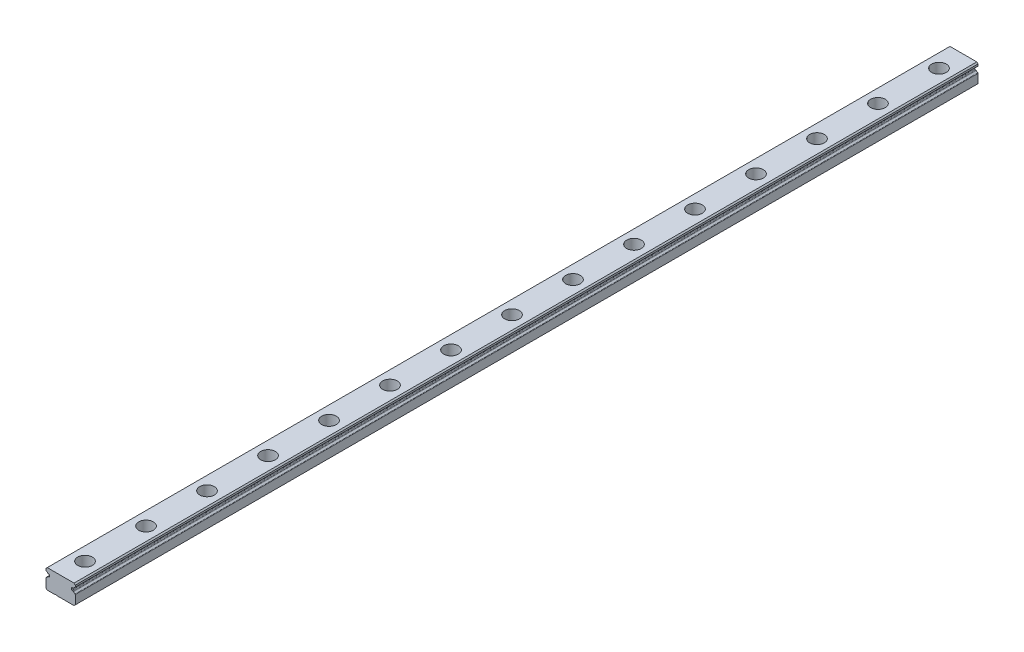
SolidWorks part; units mm, degrees
ref_plane "Front Plane" through (0, 0, 0) normal (0, 0, 1) x (1, 0, 0)
ref_plane "Top Plane" through (0, 0, 0) normal (0, 1, 0) x (1, 0, 0)
ref_plane "Right Plane" through (0, 0, 0) normal (1, 0, 0) x (0, 0, -1)
sketch "Sketch1" plane through (0, 0, 0) normal (0, 0, 1) x (1, 0, 0)
  line B0 (5.5, -8) -> (6, -7.5)
  line B1 (6, -7.5) -> (6, -3.8579)
  line B2 (5.0738, -3.0055) -> (4.7282, -2.9753)
  line B3 (4.5, -2.7262) -> (4.5, -2.2738)
  line B4 (4.7282, -2.0247) -> (5.0948, -1.9927)
  line B5 (6, -1.1746) -> (6, -0.5)
  line B6 (6, -0.5) -> (5.5, 0)
  line B7 (5.5, 0) -> (-5.5, 0)
  line B8 (-5.5, 0) -> (-6, -0.5)
  line B9 (-6, -0.5) -> (-6, -1.1746)
  line B10 (-5.0948, -1.9927) -> (-4.7282, -2.0247)
  line B11 (-4.5, -2.2738) -> (-4.5, -2.7262)
  line B12 (-4.7282, -2.9753) -> (-5.0738, -3.0055)
  line B13 (-6, -3.8579) -> (-6, -7.5)
  line B14 (-6, -7.5) -> (-5.5, -8)
  line B15 (-5.5, -8) -> (-2.4, -8)
  line B16 (-1.6, -8) -> (5.5, -8)
  line B17 (0, 0) -> (0, -8) construction
  arc B18 (6, -3.8579) -> (5.8448, -3.6266) centre (5.75, -3.8579) ccw
  arc B19 (5.2672, -3.1272) -> (5.8448, -3.6266) centre (6.3, -2.5162) ccw
  arc B20 (5.2672, -3.1272) -> (5.0738, -3.0055) centre (5.052, -3.2545) ccw
  arc B21 (4.5, -2.7262) -> (4.7282, -2.9753) centre (4.75, -2.7262) ccw
  arc B22 (4.7282, -2.0247) -> (4.5, -2.2738) centre (4.75, -2.2738) ccw
  arc B23 (5.0948, -1.9927) -> (5.2845, -1.8768) centre (5.073, -1.7436) ccw
  arc B24 (5.8448, -1.4059) -> (5.2845, -1.8768) centre (6.3, -2.5162) ccw
  arc B25 (5.8448, -1.4059) -> (6, -1.1746) centre (5.75, -1.1746) ccw
  arc B26 (-6, -1.1746) -> (-5.8448, -1.4059) centre (-5.75, -1.1746) ccw
  arc B27 (-5.2845, -1.8768) -> (-5.8448, -1.4059) centre (-6.3, -2.5162) ccw
  arc B28 (-5.2845, -1.8768) -> (-5.0948, -1.9927) centre (-5.073, -1.7436) ccw
  arc B29 (-4.5, -2.2738) -> (-4.7282, -2.0247) centre (-4.75, -2.2738) ccw
  arc B30 (-4.7282, -2.9753) -> (-4.5, -2.7262) centre (-4.75, -2.7262) ccw
  arc B31 (-5.0738, -3.0055) -> (-5.2672, -3.1272) centre (-5.052, -3.2545) ccw
  arc B32 (-5.8448, -3.6266) -> (-5.2672, -3.1272) centre (-6.3, -2.5162) ccw
  arc B33 (-5.8448, -3.6266) -> (-6, -3.8579) centre (-5.75, -3.8579) ccw
  arc B34 (-1.6, -8) -> (-2.4, -8) centre (-2, -8.3) ccw
sketch_block_instance "Block1-1"
sketch_block "Block1"
extrude "Boss-Extrude1" add sketch "Sketch1" along normal blind 370
sketch "Sketch2" plane through (0, 0, 0) normal (0, 1, 0) x (1, 0, 0)
  line L0 (0, 0) -> (0, -370) construction
  line L1 (5.5, 0) -> (-5.5, 0) construction
  line L2 (-5.5, -370) -> (5.5, -370) construction
  line L3 (5.5, -370) -> (-5.5, -370) construction
  circle A0 centre (0, -10) radius 3
  circle A1 centre (0, -10) radius 1.75
  circle A2 centre (0, -35) radius 3
  circle A3 centre (0, -35) radius 1.75
  circle A4 centre (0, -60) radius 3
  circle A5 centre (0, -60) radius 1.75
  circle A6 centre (0, -85) radius 3
  circle A7 centre (0, -85) radius 1.75
  circle A8 centre (0, -110) radius 3
  circle A9 centre (0, -110) radius 1.75
  circle A10 centre (0, -135) radius 3
  circle A11 centre (0, -135) radius 1.75
  circle A12 centre (0, -160) radius 3
  circle A13 centre (0, -160) radius 1.75
  circle A14 centre (0, -185) radius 3
  circle A15 centre (0, -185) radius 1.75
  circle A16 centre (0, -210) radius 3
  circle A17 centre (0, -210) radius 1.75
  circle A18 centre (0, -235) radius 3
  circle A19 centre (0, -235) radius 1.75
  circle A20 centre (0, -260) radius 3
  circle A21 centre (0, -260) radius 1.75
  circle A22 centre (0, -285) radius 3
  circle A23 centre (0, -285) radius 1.75
  circle A24 centre (0, -310) radius 3
  circle A25 centre (0, -310) radius 1.75
  circle A26 centre (0, -335) radius 3
  circle A27 centre (0, -335) radius 1.75
  circle A28 centre (0, -360) radius 3
  circle A29 centre (0, -360) radius 1.75
  circle A30 centre (0, -385) radius 3
  circle A31 centre (0, -385) radius 1.75
  circle A32 centre (0, -410) radius 3
  circle A33 centre (0, -410) radius 1.75
  dimension "D1" = 10
  dimension "D2" = 3.5
  dimension "D3" = 6
  dimension "D5" = 25
  dimension "D6" = 85
  dimension "D4" = 17
extrude "Cut-Extrude1" cut sketch "Sketch2" against normal through all contours A1 | A3 | A5 | A7 | A9 | A11 | A13 | A15 | A17 | A19 | A21 | A23 | A25 | A27 | A29 | A31 | A33
extrude "Cut-Extrude2" cut sketch "Sketch2<3>" against normal blind 4.5 contours A0 | A2 | A4 | A6 | A8 | A10 | A12 | A14 | A16 | A18 | A20 | A22 | A24 | A26 | A28 | A30 | A32
sketch "Sketch2<3>" plane through (0, 0, 0) normal (0, 1, 0) x (1, 0, 0) same geometry as "Sketch2"
ref_plane "Groove Center" through (0, -2.5, 0) normal (0, -1, 0) x (-1, 0, 0)
ref_plane "Rail Center" through (0, 0, 0) normal (-1, 0, 0) x (0, 0, 1)
ref_plane "Rail Mid Length Plane" through (0, 0, 185) normal (0, 0, 1) x (1, 0, 0)
